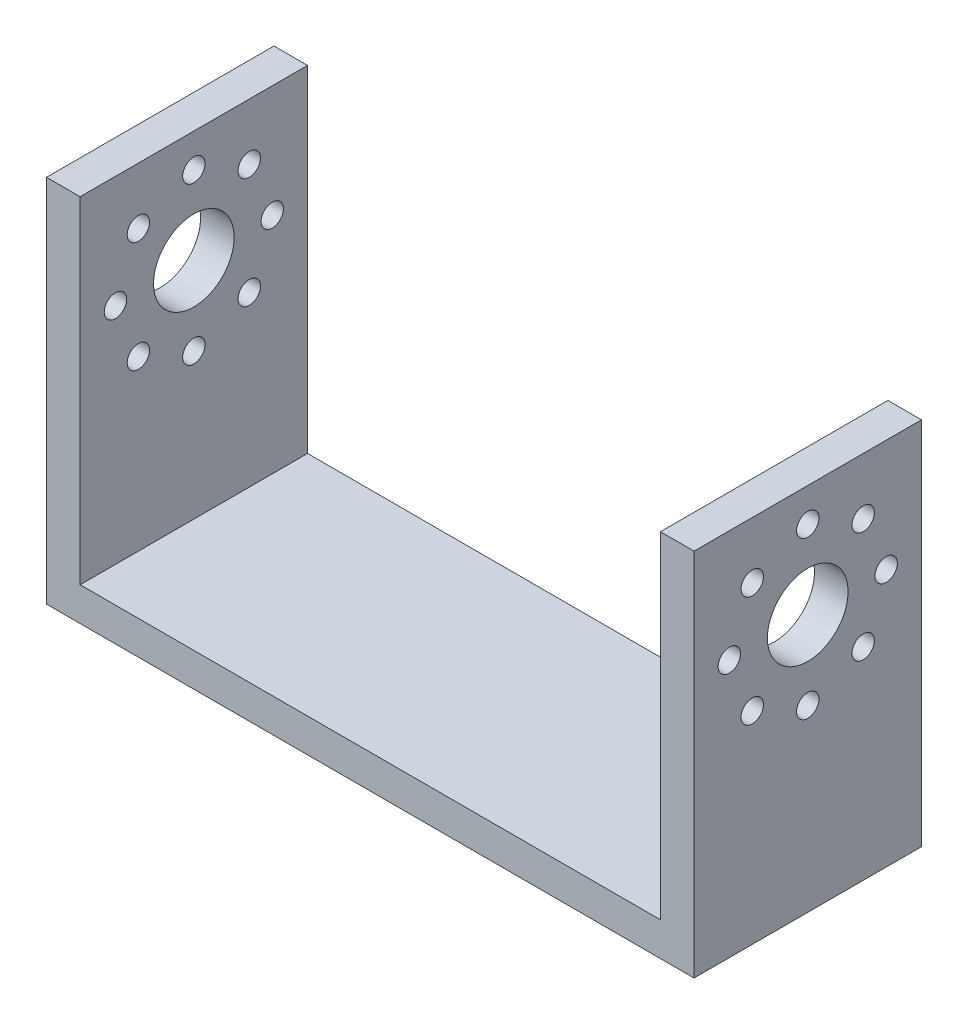
SolidWorks part; units mm, degrees
ref_plane "Front Plane" through (0, 0, 0) normal (0, 0, 1) x (1, 0, 0)
ref_plane "Top Plane" through (0, 0, 0) normal (0, 1, 0) x (1, 0, 0)
ref_plane "Right Plane" through (0, 0, 0) normal (1, 0, 0) x (0, 0, -1)
sketch "Sketch1" plane through (0, 0, 0) normal (0, 1, 0) x (1, 0, 0)
  line L1 (0, 0) -> (57.8, 0)
  line L2 (0, 0) -> (0, 20.3)
  line L3 (0, 20.3) -> (57.8, 20.3)
  line L4 (57.8, 0) -> (57.8, 20.3)
  dimension "D1" = 57.8
  dimension "D2" = 20.3
extrude "YawMount" add sketch "Sketch1" along normal blind 3
sketch "Sketch2" plane through (0, 3, 0) normal (0, 1, 0) x (1, 0, 0)
  line L0 (0, 0) -> (57.8, 0) construction
  line L1 (0, 20.3) -> (3, 20.3)
  line L2 (0, 20.3) -> (0, 0)
  line L3 (0, 0) -> (3, 0)
  line L4 (3, 20.3) -> (3, 0)
  line L6 (57.8, 20.3) -> (54.8, 20.3)
  line L7 (57.8, 20.3) -> (57.8, 0)
  line L8 (57.8, 0) -> (54.8, 0)
  line L9 (54.8, 20.3) -> (54.8, 0)
  dimension "D1" = 3
  dimension "D2" = 3
extrude "BodyConnectors" add sketch "Sketch2" along normal blind 30
sketch "Sketch3" plane through (57.8, 0, 0) normal (1, 0, 0) x (0, 0, -1)
  line L1 (0, 33) -> (20.3, 33) construction
  circle A9 centre (5.2003, 27.9497) radius 1
  circle A10 centre (10.15, 30) radius 1
  circle A11 centre (15.0997, 27.9497) radius 1
  circle A12 centre (17.15, 23) radius 1
  circle A13 centre (15.0997, 18.0503) radius 1
  circle A14 centre (10.15, 16) radius 1
  circle A15 centre (5.2003, 18.0503) radius 1
  circle A16 centre (3.15, 23) radius 1
  point P4 (10.15, 33)
  point P23 (10.15, 23)
  dimension "D1" = 2
  dimension "D2" = 20
  dimension "D3" = 7
extrude "Axle-Mounts" cut sketch "Sketch3" against normal up to surface (57.8 mm away) up to face at (0, 16.5, -10.15)
sketch "Sketch4" plane through (54.8, 0, 0) normal (-1, 0, 0) x (0, 0, 1)
  line L0 (0, 33) -> (-20.3, 33) construction
  circle A0 centre (-10.15, 23) radius 3.6
  circle A3 centre (-17.15, 23) radius 1 construction
  point P7 (-10.15, 33)
  dimension "D1" = 7.2
  dimension "D2" = 7
extrude "Axle-Counterbore" cut sketch "Sketch4" against normal up to surface and the other way up to surface up to face at (57.8, 30, -11.15) other way up to face at (0, 30, -11.15)
equation "\"srv_w\"= 40.43mm'width of Sain Smart SR319"
equation "\"D1@Sketch1\"=51.8mm + \"mnt_thick\"*2"
equation "\"srv_h\"= 40.61mm'height of Sain Smart SR319"
equation "\"srv_d\"= 20.3mm'depth of Sain Smart SR319"
equation "\"D2@Sketch1\"=\"srv_d\""
equation "\"mnt_thick\"= 3mm'thickness of bracket"
equation "\"D1@YawMount\" = \"mnt_thick\""
equation "\"D2@Sketch2\"=\"mnt_thick\""
equation "\"D1@Sketch2\"=\"mnt_thick\""
